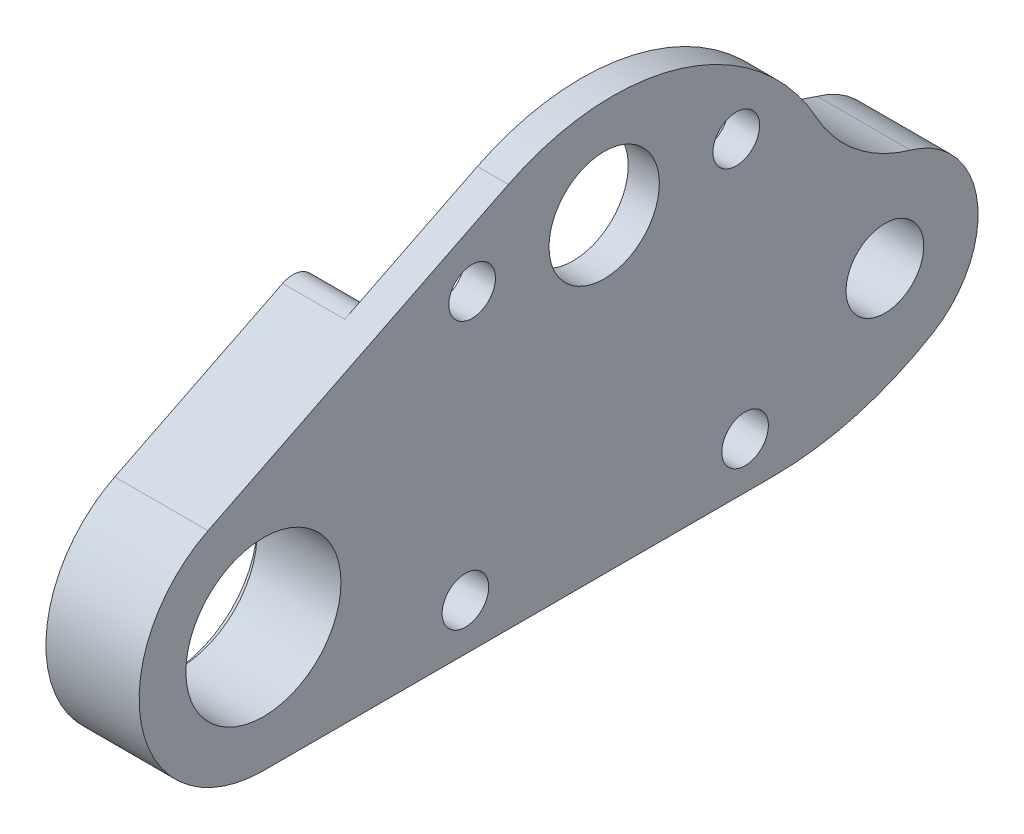
SolidWorks part; units mm, degrees
material "1060 Alloy"
ref_plane "Front Plane" through (0, 0, 0) normal (0, 0, 1) x (1, 0, 0)
ref_plane "Top Plane" through (0, 0, 0) normal (0, 1, 0) x (1, 0, 0)
ref_plane "Right Plane" through (0, 0, 0) normal (1, 0, 0) x (0, 0, -1)
sketch "Sketch27" plane through (0, 0, 0) normal (1, 0, 0) x (0, 0, -1)
  line L0 (6.4321, 49.1603) -> (25.768, 58.7953)
  line L3 (40.4317, 54) -> (23.4317, 54) construction
  line L6 (42.7889, 34) -> (10, 34)
  line L8 (0, 0) -> (60, 0) construction
  line L9 (0, 0) -> (0, 58) construction
  line L10 (0, 58) -> (60, 58) construction
  line L11 (60, 0) -> (60, 58) construction
  arc A0 (6.4321, 49.1603) -> (10, 34) centre (10, 42) ccw
  circle A1 centre (31.9317, 54) radius 12.5 construction
  arc A2 (45.6106, 52.5814) -> (25.768, 58.7953) centre (32.4579, 45.3698) ccw
  circle A3 centre (31.9317, 54) radius 3.55
  arc A4 (51.6421, 47.7709) -> (53.0905, 36.8571) centre (50, 42) cw
  circle A5 centre (10, 42) radius 4.99
  circle A6 centre (50, 42) radius 2.5
  circle A7 centre (40.4317, 54) radius 1.5
  circle A8 centre (23.4317, 54) radius 1.5
  circle A9 centre (40.4317, 54) radius 3.25 construction
  circle A10 centre (23.4317, 54) radius 3.25 construction
  arc A11 (53.0905, 36.8571) -> (42.7889, 34) centre (42.7889, 54) cw
  arc A12 (51.6421, 47.7709) -> (45.6106, 52.5814) centre (54.379, 57.3891) cw
  dimension "D9" = 6
  dimension "D10" = 5
  dimension "D11" = 15
  dimension "D12" = 9.98
  dimension "D13" = 8
  dimension "D14" = 20
  dimension "D15" = 25
  dimension "D6" = 25
  dimension "D17" = 7.1
  dimension "D16" = 3
  dimension "D19" = 6.5
  dimension "D20" = 10
  dimension "D1" = 60
  dimension "D2" = 58
  dimension "D3" = 42
  dimension "D4" = 10
  dimension "D5" = 42
  dimension "D7" = 50
  dimension "D8" = 12
  dimension "D18" = 8.5
extrude "Boss-Extrude1" add sketch "Sketch27" along normal blind 6
sketch "Sketch47" plane through (0, 0, 0) normal (-1, 0, 0) x (0, 0, 1)
  circle A0 centre (-10, 42) radius 5.605
  dimension "D1" = 11.21
extrude "Cut-Extrude8" cut sketch "Sketch47" against normal blind 0.6
sketch "Sketch48" plane through (0, 0, 0) normal (-1, 0, 0) x (0, 0, 1)
  line L1 (-25.768, 58.7953) -> (-6.4321, 49.1603) construction
  line L2 (-46.7042, 50.9784) -> (-37.7377, 64.7597)
  line L4 (-37.7377, 64.7597) -> (-17.2355, 54.5436)
  arc A0 (-44.004, 50.5703) -> (-19.402, 53.2863) centre (-31.9317, 54) ccw
  arc A1 (-44.004, 50.5703) -> (-46.7042, 50.9784) centre (-45.4469, 50.1604) ccw
  arc A2 (-19.402, 53.2863) -> (-17.2355, 54.5436) centre (-17.9044, 53.201) cw
  arc A3 (-51.6421, 47.7709) -> (-45.6106, 52.5814) centre (-54.379, 57.3891) ccw construction
  arc A4 (-25.768, 58.7953) -> (-45.6106, 52.5814) centre (-32.4579, 45.3698) ccw construction
  dimension "D1" = 12.55
  dimension "D2" = 1.5
  dimension "D3" = 1.5
extrude "Cut-Extrude10" cut sketch "Sketch48" against normal blind 4
sketch "Sketch49" plane through (0, 0, 0) normal (-1, 0, 0) x (0, 0, 1)
  line L0 (-44, 34) -> (-20, 34)
  line L1 (-44, 34) -> (-44, 40)
  line L2 (-20, 34) -> (-20, 40)
  line L3 (-44, 40) -> (-20, 40)
  line L4 (-10, 34) -> (-42.7889, 34) construction
  circle A0 centre (-50, 42) radius 2.5 construction
  dimension "D1" = 6
  dimension "D2" = 24
  dimension "D3" = 6
extrude "Cut-Extrude11" cut sketch "Sketch49" against normal blind 3
sketch "Sketch50" plane through (0, 0, 0) normal (-1, 0, 0) x (0, 0, 1)
  circle A0 centre (-44, 40) radius 1.5
  circle A1 centre (-20, 40) radius 1.5
  dimension "D1" = 3
extrude "Cut-Extrude12" cut sketch "Sketch50" against normal up to surface (3 mm away) up to face at (3, 36.4055, -34.1578)
fillet "Fillet1" radius 3 4 edges at (1.5, 38.5, -44) (1.5, 38.5, -20) (1.5, 40, -21.5) (1.5, 40, -42.5)
sketch "Sketch51" plane through (3, 0, 0) normal (-1, 0, 0) x (0, 0, 1)
  line L0 (-42.7889, 34) -> (-20, 34) construction
  line L1 (-44, 36.6459) -> (-44, 34.0367) construction
  line L2 (-20, 34) -> (-20, 36.6459) construction
  circle A0 centre (-41, 37) radius 1.5
  circle A1 centre (-23, 37) radius 1.5
  dimension "D1" = 3
  dimension "D2" = 3
  dimension "D3" = 3
  dimension "D4" = 3
  dimension "D5" = 3
extrude "Cut-Extrude13" cut sketch "Sketch51" against normal up to next
